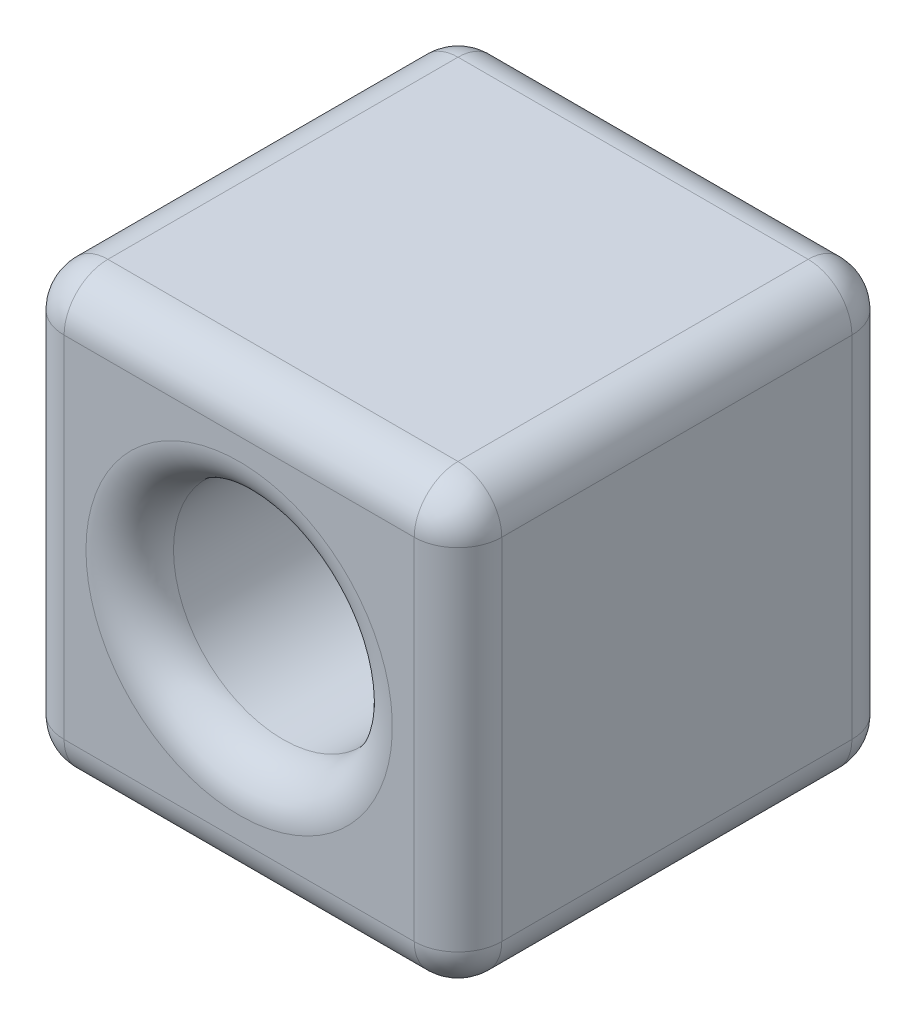
SolidWorks part; units mm, degrees
ref_plane "Front Plane" through (0, 0, 0) normal (0, 0, 1) x (1, 0, 0)
ref_plane "Top Plane" through (0, 0, 0) normal (0, 1, 0) x (1, 0, 0)
ref_plane "Right Plane" through (0, 0, 0) normal (1, 0, 0) x (0, 0, -1)
sketch "Sketch2" plane through (0, 0, 0) normal (0, 1, 0) x (1, 0, 0)
  line L1 (0, 0) -> (100, 0)
  line L2 (0, 0) -> (0, 100)
  line L3 (0, 100) -> (100, 100)
  line L4 (100, 0) -> (100, 100)
  dimension "D1" = 100
  dimension "D2" = 100
extrude "Boss-Extrude1" add sketch "Sketch2" along normal blind 100
sketch "Sketch3" plane through (0, 0, 0) normal (0, 0, 1) x (1, 0, 0)
  line L0 (0, 100) -> (0, 0) construction
  line L3 (0, 0) -> (100, 0) construction
  circle A0 centre (50, 50) radius 25
  dimension "D1" = 50
  dimension "D3" = 50
  dimension "D2" = 50
extrude "Cut-Extrude1" cut sketch "Sketch3" against normal blind 100 contours A0
fillet "Fillet1" radius 10 5 edges at (0, 50, 0) (50, 100, 0) (100, 50, 0) (50, 0, 0) (75, 50, 0)
fillet "Fillet2" radius 10 5 edges at (100, 50, -100) (50, 100, -100) (0, 50, -100) (50, 0, -100) (75, 50, -100)
fillet "Fillet3" radius 10 6 edges at (97.0711, 97.0711, -2.9289) (97.0711, 97.0711, -97.0711) (97.0711, 2.9289, -2.9289) (97.0711, 2.9289, -97.0711) (100, 100, -50) (100, 0, -50)
fillet "Fillet4" radius 10 6 edges at (2.9289, 2.9289, -97.0711) (2.9289, 2.9289, -2.9289) (2.9289, 97.0711, -97.0711) (2.9289, 97.0711, -2.9289) (0, 0, -50) (0, 100, -50)
